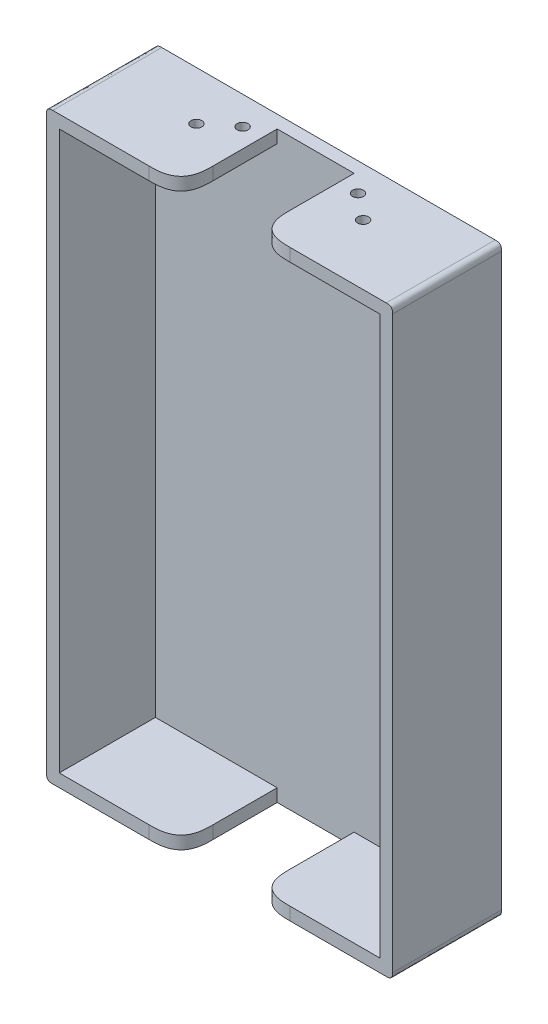
SolidWorks part; units mm, degrees
ref_plane "前视基准面" through (0, 0, 0) normal (0, 0, 1) x (1, 0, 0)
ref_plane "上视基准面" through (0, 0, 0) normal (0, 1, 0) x (1, 0, 0)
ref_plane "右视基准面" through (0, 0, 0) normal (1, 0, 0) x (0, 0, -1)
sketch "草图1" plane through (0, 0, 0) normal (0, 0, 1) x (1, 0, 0)
  line L0 (-27, 45.5) -> (27, 45.5)
  line L1 (-25, 43.5) -> (25, 43.5)
  line L2 (-25, 43.5) -> (-25, -43.5)
  line L3 (-25, -43.5) -> (25, -43.5)
  line L4 (25, 43.5) -> (25, -43.5)
  line L5 (-25, 43.5) -> (25, -43.5) construction
  line L6 (-25, -43.5) -> (25, 43.5) construction
  line L7 (27, 45.5) -> (27, -45.5)
  line L8 (-27, -45.5) -> (27, -45.5)
  line L9 (-27, 45.5) -> (-27, -45.5)
  point P0 (0, 0)
  dimension "D1" = 50
  dimension "D2" = 87
  dimension "D3" = 2
extrude "凸台-拉伸1" add sketch "草图1" along normal blind 17
sketch "草图2" plane through (0, 0, 0) normal (0, 0, -1) x (-1, 0, 0)
  line L4 (27, -45.5) -> (27, 45.5)
  line L5 (27, 45.5) -> (-27, 45.5)
  line L6 (-27, 45.5) -> (-27, -45.5)
  line L7 (-27, -45.5) -> (27, -45.5)
  line L8 (27, -45.5) -> (27, 45.5)
  line L9 (27, 45.5) -> (-27, 45.5)
  line L10 (-27, 45.5) -> (-27, -45.5)
  line L11 (-27, -45.5) -> (27, -45.5)
  dimension "D1" = 0
extrude "凸台-拉伸2" add sketch "草图2" against normal blind 2
sketch "草图3" plane through (0, 0, 17) normal (0, 0, 1) x (1, 0, 0)
  line L1 (-6, 49.3155) -> (6, 49.3155)
  line L2 (-6, 49.3155) -> (-6, -49.3155)
  line L3 (-6, -49.3155) -> (6, -49.3155)
  line L4 (6, 49.3155) -> (6, -49.3155)
  line L5 (-6, 49.3155) -> (6, -49.3155) construction
  line L6 (-6, -49.3155) -> (6, 49.3155) construction
  point P0 (0, 0)
  dimension "D1" = 12
extrude "切除-拉伸1" cut sketch "草图3" against normal up to surface (15 mm away) up to face at (0, 0, 2)
sketch "草图5" plane through (0, 45.5, 0) normal (0, 1, 0) x (1, 0, 0)
  circle A0 centre (-9, -4.4) radius 0.85
  circle A1 centre (-13, -7.6) radius 0.85
  circle A2 centre (9, -4.4) radius 0.85
  circle A3 centre (13, -7.6) radius 0.85
  dimension "D1" = 1.7
  dimension "D2" = 1.7
  dimension "D3" = 1.7
  dimension "D4" = 1.7
extrude "切除-拉伸2" cut sketch "草图5" against normal blind 11
fillet "圆角1" radius 1 4 edges at (-27, -45.5, 8.5) (27, -45.5, 8.5) (27, 45.5, 8.5) (-27, 45.5, 8.5) curvature continuous yes
fillet "圆角2" radius 5 4 edges at (6, -44.5, 17) (-6, -44.5, 17) (6, 44.5, 17) (-6, 44.5, 17) curvature continuous yes
